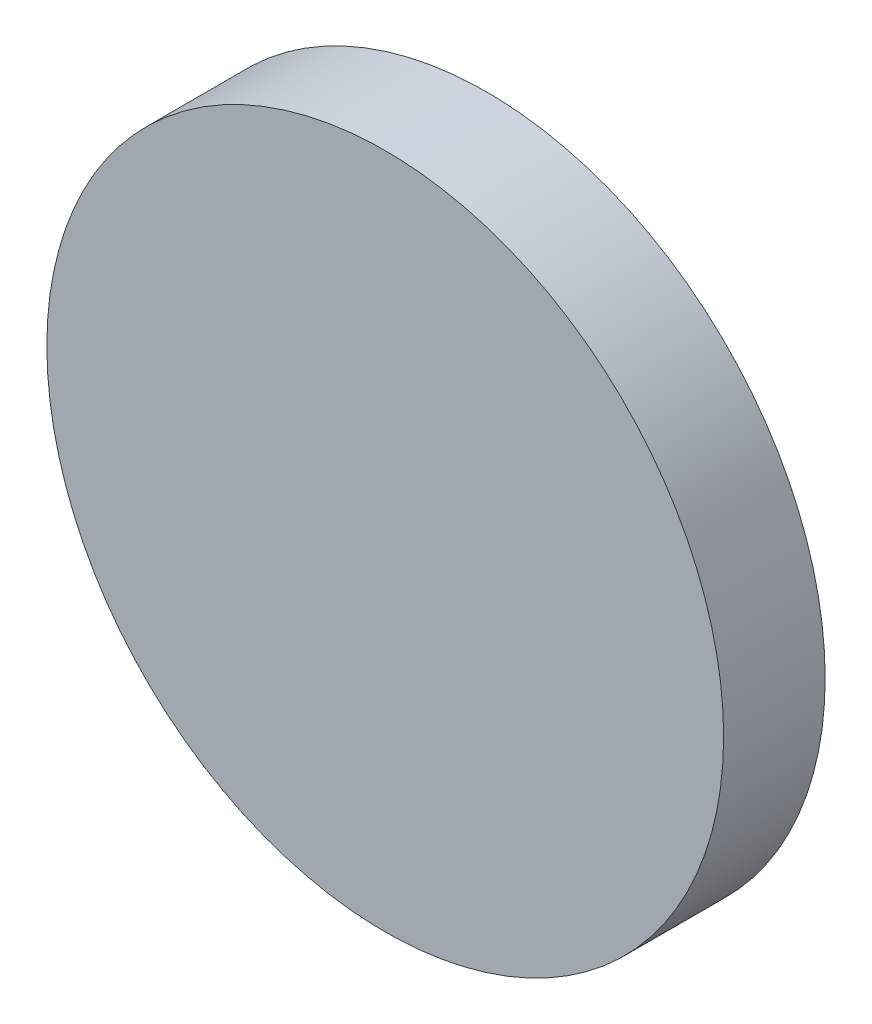
SolidWorks part; units mm, degrees
ref_plane "Front Plane" through (0, 0, 0) normal (0, 0, 1) x (1, 0, 0)
ref_plane "Top Plane" through (0, 0, 0) normal (0, 1, 0) x (1, 0, 0)
ref_plane "Right Plane" through (0, 0, 0) normal (1, 0, 0) x (0, 0, -1)
sketch "SK_Horn" plane through (0, 0, 0) normal (0, 0, 1) x (1, 0, 0)
  circle A0 centre (0, 0) radius 10
  dimension "D1_SK_Horn" = 20
extrude "Horn" add sketch "SK_Horn" along normal blind 3
ref_axis "AX_Joint" through (0, 0, -0.15) along (0, 0, 1)
